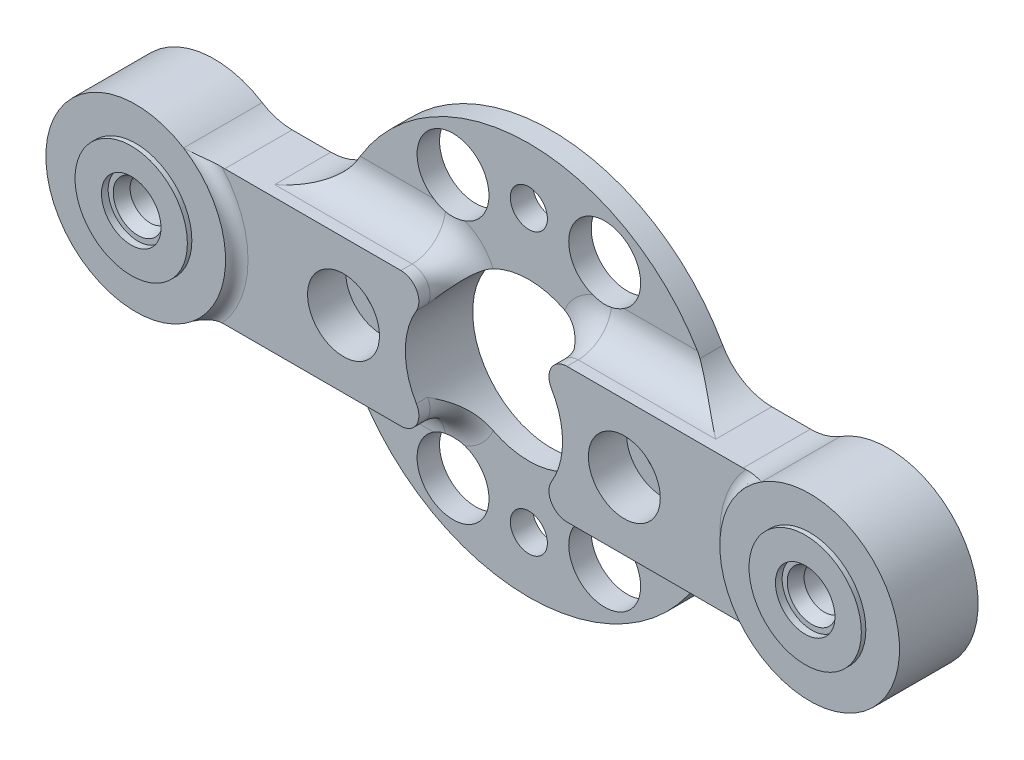
SolidWorks part; units mm, degrees
ref_plane "前视基准面" through (0, 0, 0) normal (0, 0, 1) x (1, 0, 0)
ref_plane "上视基准面" through (0, 0, 0) normal (0, 1, 0) x (1, 0, 0)
ref_plane "右视基准面" through (0, 0, 0) normal (1, 0, 0) x (0, 0, -1)
other "Configuration Table"
sketch "草图1" plane through (0, 0, 0) normal (0, 0, 1) x (1, 0, 0)
  line L0 (-23.0718, 6) -> (23.0718, 6)
  line L1 (-23.0718, -6) -> (23.0718, -6)
  arc A0 (25.7365, -6.7692) -> (25.7365, 6.7692) centre (30, 0) ccw
  arc A1 (-25.7365, 6.7692) -> (-25.7365, -6.7692) centre (-30, 0) ccw
  arc A2 (23.0718, 6) -> (25.7365, 6.7692) centre (23.0718, 11) ccw
  arc A3 (25.7365, -6.7692) -> (23.0718, -6) centre (23.0718, -11) ccw
  arc A4 (-25.7365, -6.7692) -> (-23.0718, -6) centre (-23.0718, -11) cw
  arc A5 (-25.7365, 6.7692) -> (-23.0718, 6) centre (-23.0718, 11) ccw
  dimension "D1" = 5
extrude "凸台-拉伸1" add sketch "草图1" along normal blind 6
sketch "草图2" plane through (0, 0, 6) normal (0, 0, 1) x (1, 0, 0)
  circle A0 centre (-30, 0) radius 8
  circle A1 centre (30, 0) radius 8
extrude "凸台-拉伸2" add sketch "草图2" along normal blind 1
fillet "圆角1" radius 1 2 edges at (22, 0, 6) (-22, 0, 6)
sketch "草图4" plane through (0, 0, 7) normal (0, 0, 1) x (1, 0, 0)
  circle A0 centre (-30, 0) radius 1.8
  circle A1 centre (30, 0) radius 1.8
  arc A2 (-25.7365, 6.7692) -> (-25.7365, -6.7692) centre (-30, 0) ccw construction
  arc A3 (25.7365, -6.7692) -> (25.7365, 6.7692) centre (30, 0) ccw construction
extrude "切除-拉伸1" cut sketch "草图4" against normal up to surface (7 mm away) up to face at (0, 0, 0)
sketch "草图5" plane through (0, 0, 0) normal (0, 0, 1) x (1, 0, 0)
  circle A0 centre (0, 0) radius 17.5
extrude "凸台-拉伸4" add sketch "草图5" along normal blind 2
fillet "圆角2" radius 5 4 edges at (-16.4393, -6, 1) (16.4393, -6, 1) (16.4393, 6, 1) (-16.4393, 6, 1)
sketch "草图6" plane through (0, 0, 6) normal (0, 0, 1) x (1, 0, 0)
  circle A0 centre (0, 0) radius 7
extrude "切除-拉伸2" cut sketch "草图6" against normal up to surface (6 mm away) up to face at (0, 0, 0)
fillet "圆角3" radius 1.6 4 edges at (-3.6056, -6, 4) (3.6056, -6, 4) (-3.6056, 6, 4) (3.6056, 6, 4)
fillet "圆角4" radius 3 8 edges at (5.9982, -5.1906, 2) (-5.9982, -5.1906, 2) (-5.9982, 5.1906, 2) (5.9982, 5.1906, 2) (13.5085, -6, 2) (-13.5085, -6, 2) (-13.5085, 6, 2) (13.5085, 6, 2)
sketch "草图8" plane through (0, 0, 6) normal (0, 0, 1) x (1, 0, 0)
  circle A1 centre (6.75, -11.6913) radius 3.2
  circle A2 centre (-6.75, -11.6913) radius 3.2
  circle A4 centre (-6.75, 11.6913) radius 3.2
  circle A5 centre (6.75, 11.6913) radius 3.2
  point P14 (0, 0)
extrude "切除-拉伸3" cut sketch "草图8" against normal up to surface (6 mm away) up to face at (7, 0, 0)
sketch "草图9" plane through (0, 0, 6) normal (0, 0, 1) x (1, 0, 0)
  circle A0 centre (12.5, 0) radius 1.65
  circle A1 centre (0, -12.5) radius 1.65
  circle A2 centre (-12.5, 0) radius 1.65
  circle A3 centre (0, 12.5) radius 1.65
  point P11 (0, 0)
  dimension "D1" = 4
extrude "切除-拉伸4" cut sketch "草图9" against normal up to surface (6 mm away) up to face at (9.95, 11.6913, 0)
sketch "草图10" plane through (0, 0, 6) normal (0, 0, 1) x (1, 0, 0)
  circle A0 centre (-12.5, 0) radius 3.2
  circle A1 centre (12.5, 0) radius 3.2
extrude "切除-拉伸5" cut sketch "草图10" against normal blind 3.4
sketch "草图11" plane through (0, 0, 7) normal (0, 0, 1) x (1, 0, 0)
  circle A0 centre (-30, 0) radius 1.8 construction
  circle A1 centre (-30, 0) radius 1.8
  circle A2 centre (30, 0) radius 1.8 construction
  circle A3 centre (30, 0) radius 1.8
  circle A4 centre (-30, 0) radius 5
  circle A5 centre (30, 0) radius 5
extrude "凸台-拉伸5" add sketch "草图11" along normal blind 0.4
sketch "草图12" plane through (0, 0, 7.4) normal (0, 0, 1) x (1, 0, 0)
  circle A0 centre (-30, 0) radius 2.65
  circle A1 centre (30, 0) radius 2.65
extrude "切除-拉伸6" cut sketch "草图12" against normal blind 0.6
chamfer "倒角1" distance 0.4 angle 70 2 edges at (31.8, 0, 6.8) (-28.2, 0, 6.8) first distance on face at (32.65, 0, 6.8) first distance on face at (-27.35, 0, 6.8)
